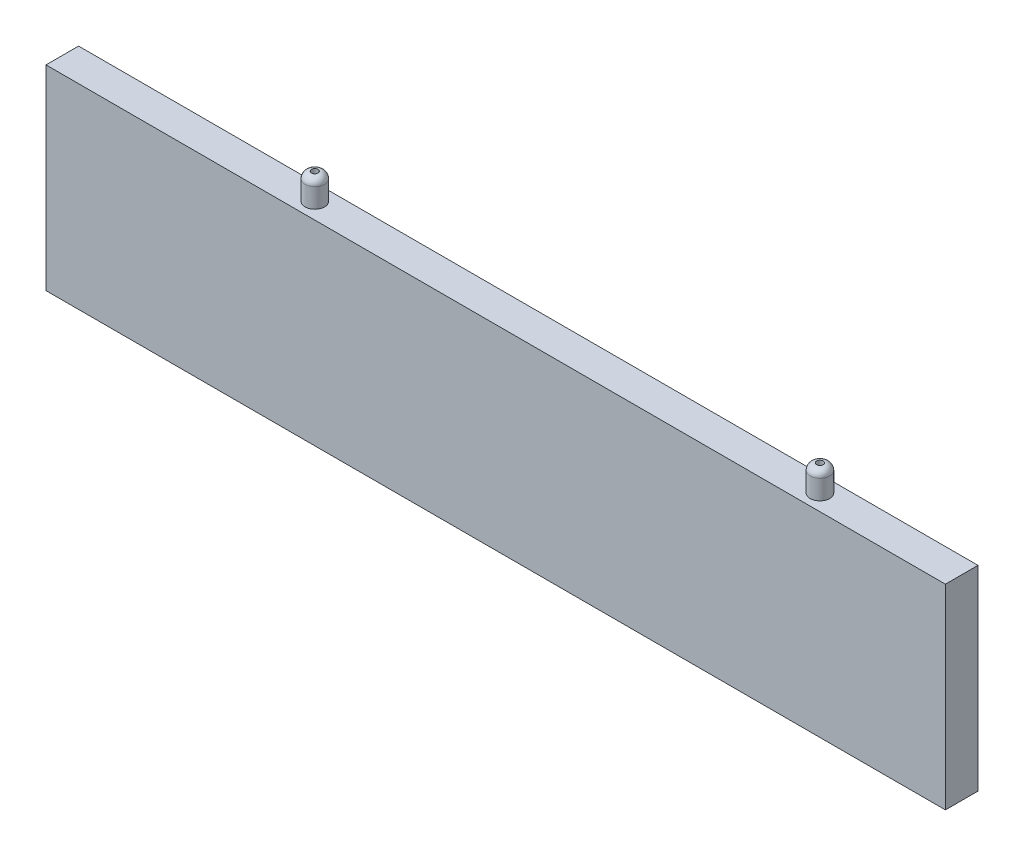
SolidWorks part; units mm, degrees
ref_plane "Plan de face" through (0, 0, 0) normal (0, 0, 1) x (1, 0, 0)
ref_plane "Plan de dessus" through (0, 0, 0) normal (0, 1, 0) x (1, 0, 0)
ref_plane "Plan de droite" through (0, 0, 0) normal (1, 0, 0) x (0, 0, -1)
sketch "Esquisse1" plane through (0, 0, 0) normal (0, 0, 1) x (1, 0, 0)
  line L1 (-77.5, 15) -> (77.5, 15)
  line L2 (-77.5, 15) -> (-77.5, -15)
  line L3 (-77.5, -15) -> (77.5, -15)
  line L4 (77.5, 15) -> (77.5, -15)
  line L5 (-77.5, 15) -> (77.5, -15) construction
  line L6 (-77.5, -15) -> (77.5, 15) construction
  point P0 (0, 0)
  dimension "D1" = 155
  dimension "D2" = 30
extrude "Boss.-Extru.1" add sketch "Esquisse1" along normal blind 5
sketch "Esquisse2" plane through (0, 15, 0) normal (0, 1, 0) x (1, 0, 0)
  line L0 (77.5, -5) -> (-77.5, -5) construction
  line L3 (0, 0) -> (0, -15.0224) construction
  circle A0 centre (-38.75, -2.5) radius 1.5
  circle A1 centre (38.75, -2.5) radius 1.5
  circle A2 centre (-38.75, -2.5) radius 0.5
  circle A3 centre (38.75, -2.5) radius 0.5
  dimension "D1" = 3
  dimension "D4" = 1
  dimension "D5" = 1
  dimension "D2" = 2.5
  dimension "D3" = 38.75
extrude "Boss.-Extru.2" add sketch "Esquisse2" along normal blind 4
fillet "Congé1" radius 1 2 edges at (38.75, 19, 1) (-38.75, 19, 4)
sketch "Esquisse4" plane through (77.5, 0, 0) normal (1, 0, 0) x (0, 0, -1)
  line L4 (0, -15) -> (0, 15)
  line L5 (0, 15) -> (-5, 15)
  line L6 (-5, 15) -> (-5, -15)
  line L7 (-5, -15) -> (0, -15)
  line L8 (0, -15) -> (0, 15)
  line L9 (0, 15) -> (-5, 15)
  line L10 (-5, 15) -> (-5, -15)
  line L11 (-5, -15) -> (0, -15)
  dimension "D1" = 0
extrude "Enlèv. mat.-Extru.2" cut sketch "Esquisse4" against normal blind 17
